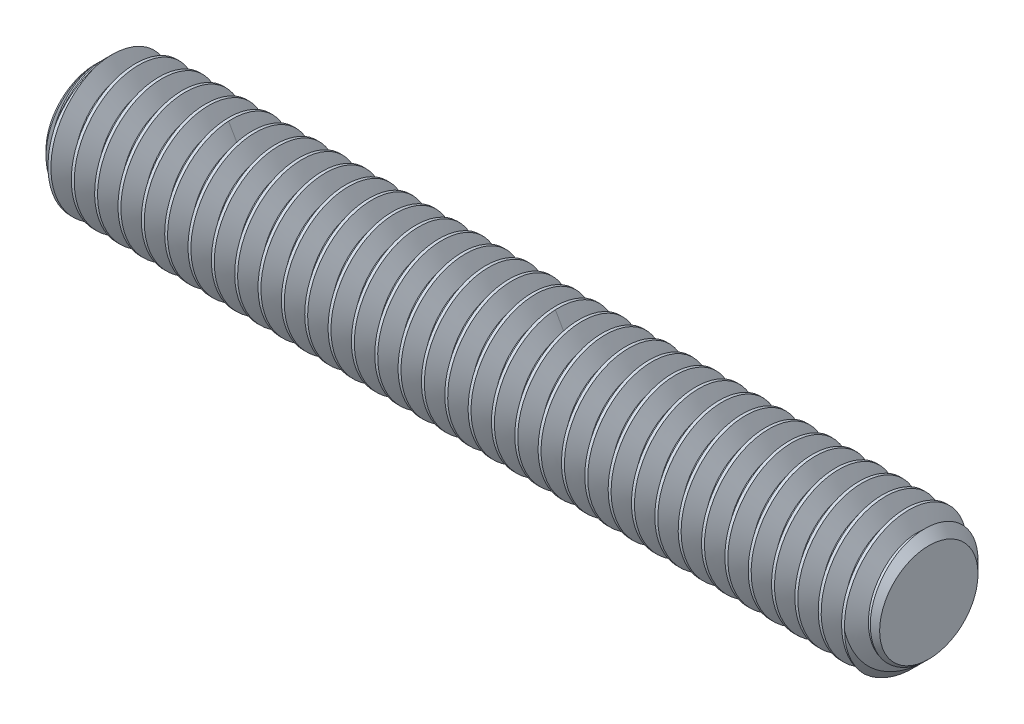
SolidWorks part; units mm, degrees
ref_plane "Front Plane" through (0, 0, 0) normal (0, 0, 1) x (1, 0, 0)
ref_plane "Top Plane" through (0, 0, 0) normal (0, 1, 0) x (1, 0, 0)
ref_plane "Right Plane" through (0, 0, 0) normal (1, 0, 0) x (0, 0, -1)
sketch "Sketch1" plane through (0, 0, 0) normal (0, 0, 1) x (1, 0, 0)
  line L0 (-12.5, 0) -> (12.5, 0) construction
  line L1 (12.5, 2) -> (12.5, -2) construction
  line L2 (-12.5, 2) -> (-12.5, -2) construction
  line L3 (12.5, 2) -> (2, 2) construction
  line L4 (-12.5, 2) -> (-11.8, 2) construction
  point P6 (10.05, -2)
  point P9 (-4.5, 0)
  point P10 (4.5, 0)
  dimension "Thread Diameter" = 4
  dimension "Length" = 25
  dimension "D1" = 2.45
  dimension "Segment Length" = 10.5
  dimension "D2" = 8
  dimension "D3" = 8
  dimension "Thread Pitch" = 0.7
sketch "Sketch2" plane through (0, 0, 0) normal (1, 0, 0) x (0, 0, -1)
  circle A0 centre (0, 0) radius 2
extrude "Boss-Extrude1" add sketch "Sketch2" against normal up to vertex (12.5 mm away) and the other way up to vertex (12.5 mm away) up to point (-12.5, 0, 0) other way up to point (12.5, 0, 0)
chamfer "Chamfer1" distance 0.525 angle 45 2 edges at (-12.5, 0, -2) (12.5, 0, -2)
sketch "Drawing1" plane through (0, 0, 0) normal (1, 0, 0) x (0, 0, -1)
  circle A0 centre (0, 0) radius 2
sketch "Sketch3" plane through (12.5, 0, 0) normal (1, 0, 0) x (0, 0, -1)
  circle A1 centre (0, 0) radius 2
  circle A2 centre (0, 0) radius 2
  dimension "D1" = 0
curve "Helix/Spiral1" pitch 0.7 height 11.2 turns 16 parameters "Pitch"=0.7
sketch "Sketch4" plane through (0, 0, 0) normal (0, 0, 1) x (1, 0, 0)
  line L0 (12.4562, 2.0758) -> (12.8062, 1.4696) construction
  line L1 (12.8062, 1.4696) -> (13.1562, 2.0758) construction
  line L2 (13.1562, 2.0758) -> (12.4562, 2.0758) construction
  line L3 (12.8062, 2.0758) -> (12.8062, 2) construction
  line L4 (12.8062, 1.4696) -> (12.8062, 1.5453) construction
  line L5 (12.7625, 1.5453) -> (12.85, 1.5453) construction
  line L6 (12.5, 2) -> (13.1125, 2) construction
  line L7 (12.7625, 1.5453) -> (12.4781, 2.0379)
  line L8 (12.7625, 1.5453) -> (12.85, 1.5453)
  line L9 (12.4781, 2.0379) -> (13.1344, 2.0379)
  line L10 (13.1344, 2.0379) -> (12.85, 1.5453)
  point P13 (12.8062, 2.0379)
  dimension "D2" = 0.0875
sweep "Cut-Sweep3" cut profiles "Sketch4" path "Helix/Spiral1" align with end faces yes
pattern_linear "LPattern1" count 4 spacing 9.8 along (1, 0, 0) of "Cut-Sweep3"
equation "\"D3@Helix/Spiral1\"=\"Pitch@Helix/Spiral1\"+\"Segment Length@Sketch1\""
equation "\"D1@Chamfer1\" = \"Pitch@Helix/Spiral1\"*.75"
equation "\"D1@Sketch4\" = \"Pitch@Helix/Spiral1\""
equation "\"D2@Sketch4\" = \"D1@Sketch4\"/8"
equation "\"D1@Sketch1\" = \"Pitch@Helix/Spiral1\"*3.50"
equation "\"Segment Length@Sketch1\"=\"Pitch@Helix/Spiral1\"*15"
equation "\"D1@LPattern1\"=(\"Length@Sketch1\"/(\"Segment Length@Sketch1\"-\"Pitch@Helix/Spiral1\"))+1"
equation "\"D3@LPattern1\"=\"Segment Length@Sketch1\"-\"Pitch@Helix/Spiral1\""
equation "\"D2@Sketch1\"=\"Thread Diameter@Sketch1\"*2"
equation "\"D3@Sketch1\"=\"Thread Diameter@Sketch1\"*2"
equation "\"Pitch@Helix/Spiral1\"=\"Thread Pitch@Sketch1\""
